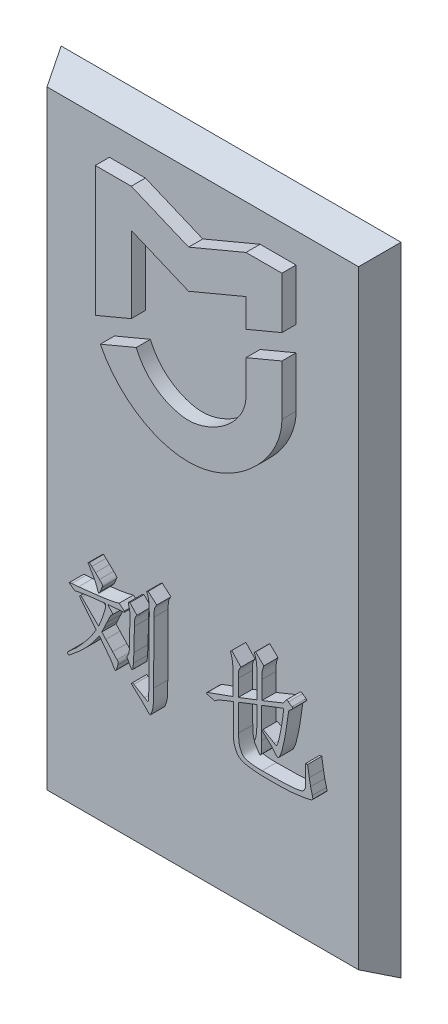
SolidWorks part; units mm, degrees
ref_plane "前视基准面" through (0, 0, 0) normal (0, 0, 1) x (1, 0, 0)
ref_plane "上视基准面" through (0, 0, 0) normal (0, 1, 0) x (1, 0, 0)
ref_plane "右视基准面" through (0, 0, 0) normal (1, 0, 0) x (0, 0, -1)
other "Configuration Table"
sketch "草图1" plane through (0, 0, 0) normal (0, 0, 1) x (1, 0, 0)
  line L18 (-12, -22.5) -> (12, -22.5)
  line L19 (-12, -22.5) -> (-12, 22.5)
  line L20 (-12, 22.5) -> (12, 22.5)
  line L21 (12, -22.5) -> (12, 22.5)
  line L22 (-12, -22.5) -> (12, 22.5) construction
  line L23 (-12, 22.5) -> (12, -22.5) construction
  point P0 (0, 0)
  dimension "D2" = 45
  dimension "D1" = 24
ref_plane "基准面1" through (0, 0, 2) normal (0, 0, 1) x (1, 0, 0)
sketch "草图2" plane through (0, 0, 2) normal (0, 0, 1) x (1, 0, 0)
  line L0 (-12, 22.5) -> (12, 22.5) construction
  line L1 (-11, -21.5) -> (11, -21.5)
  line L2 (-11, -21.5) -> (-11, 21.5)
  line L3 (-11, 21.5) -> (11, 21.5)
  line L4 (11, -21.5) -> (11, 21.5)
  line L5 (-11, -21.5) -> (11, 21.5) construction
  line L6 (-11, 21.5) -> (11, -21.5) construction
  line L7 (12, -22.5) -> (12, 22.5) construction
  point P0 (0, 0)
  dimension "D1" = 1
  dimension "D2" = 1
loft "放样1" add profiles "草图1", "草图2" connector at (-12, -22.5, 0) connector at (-11, -21.5, 2)
sketch "草图3" plane through (0, 0, 2) normal (0, 0, 1) x (1, 0, 0)
  line L0 (69.5095, 236.7647) -> (402.8428, 236.7647) construction
  line L1 (-25.2949, 7.1) -> (-27.616, 7.1) construction
  line L2 (0, 0) -> (0, 41.0504) construction
  line L3 (-6.59, 10.2338) -> (-6.59, 19.4)
  line L4 (-6.59, 19.4) -> (-4.05, 19.4)
  line L5 (-4.05, 19.4) -> (0, 17.7)
  line L6 (0, 17.7) -> (4.05, 19.4)
  line L7 (4.05, 19.4) -> (6.59, 19.4)
  line L8 (6.59, 19.4) -> (6.59, 15.7662)
  line L9 (6.59, 15.7662) -> (4.05, 14.7)
  line L10 (4.05, 14.7) -> (4.05, 16.7)
  line L11 (4.05, 16.7) -> (0, 15)
  line L12 (0, 15) -> (-4.05, 16.7)
  line L13 (-4.05, 16.7) -> (-4.05, 11.3)
  line L14 (-4.05, 11.3) -> (-6.59, 10.2338)
  line L16 (4.05, 12.9648) -> (6.59, 14.0309)
  line L17 (4.05, 14.7) -> (0, 14.7) construction
  line L18 (-4.05, 11.3) -> (0, 11.3) construction
  line L19 (11, 21.5) -> (-11, 21.5) construction
  line L20 (6.59, 14.0309) -> (6.59, 10.4595)
  line L21 (4.05, 12.9648) -> (4.05, 10.5907)
  line L22 (-3.6952, 9.7137) -> (-6.2352, 8.6475)
  line L23 (0, 7.1) -> (0, 4.56) construction
  line L24 (-23.4312, 4.56) -> (-28.3926, 4.56) construction
  spline S0 degree 3 poles (-3.6952, 9.7137) (-2.9407, 7.8881) (-0.8013, 7.0038) (2.0445, 7.2644) (4.05, 9.0403) (4.05, 10.5907) knots 0 0 0 0 0.291621 0.391621 1 1 1 1
  spline S1 degree 3 poles (-6.2352, 8.6475) (-4.8708, 5.9474) (1.073, 2.3429) (6.59, 7.9387) (6.59, 10.4595) knots 0 0 0 0 0.499283 1 1 1 1
  point P33 (0, 4.56)
  dimension "D9" = 1.6
  dimension "D1" = 4.05
  dimension "D2" = 6.5
  dimension "D3" = 0.3
  dimension "D4" = 2.7
  dimension "D5" = 1.7
  dimension "D6" = 2.54
  dimension "D7" = 5.4
  dimension "D8" = 7.9
extrude "凸台-拉伸2" add sketch "草图3" along normal blind 1
sketch "草图4" plane through (0, 0, 2) normal (0, 0, 1) x (1, 0, 0)
  line L6 (-11, -11) -> (11, -11) construction
  line L7 (-11, -21.5) -> (-11, 21.5) construction
  line L8 (11, -21.5) -> (11, 21.5) construction
  text T0 "刘也" font "汉仪长仿宋体" height 5.5
  dimension "D1" = 11
extrude "凸台-拉伸3" add sketch "草图4" along normal blind 1
sketch "草图5" plane through (0, 0, 0) normal (0, 0, -1) x (-1, 0, 0)
  line L0 (-12, -22.5) -> (-12, 22.5) construction
  line L1 (-12, 22.5) -> (12, 22.5) construction
  line L2 (12, -22.5) -> (-12, -22.5) construction
  line L3 (12, 22.5) -> (12, -22.5) construction
  circle A0 centre (-8, 14.5) radius 0.4
  circle A1 centre (8, 14.5) radius 0.4
  circle A2 centre (-8, -14.5) radius 0.4
  circle A3 centre (8, -14.5) radius 0.4
  point P8 (0, 0)
  point P9 (0, 0)
  point P10 (0, 0)
  point P11 (0, 0)
  dimension "D5" = 0.8
  dimension "D1" = 4
  dimension "D2" = 8
  dimension "D3" = 8
  dimension "D4" = 4
extrude "切除-拉伸1" cut sketch "草图5" against normal blind 1
